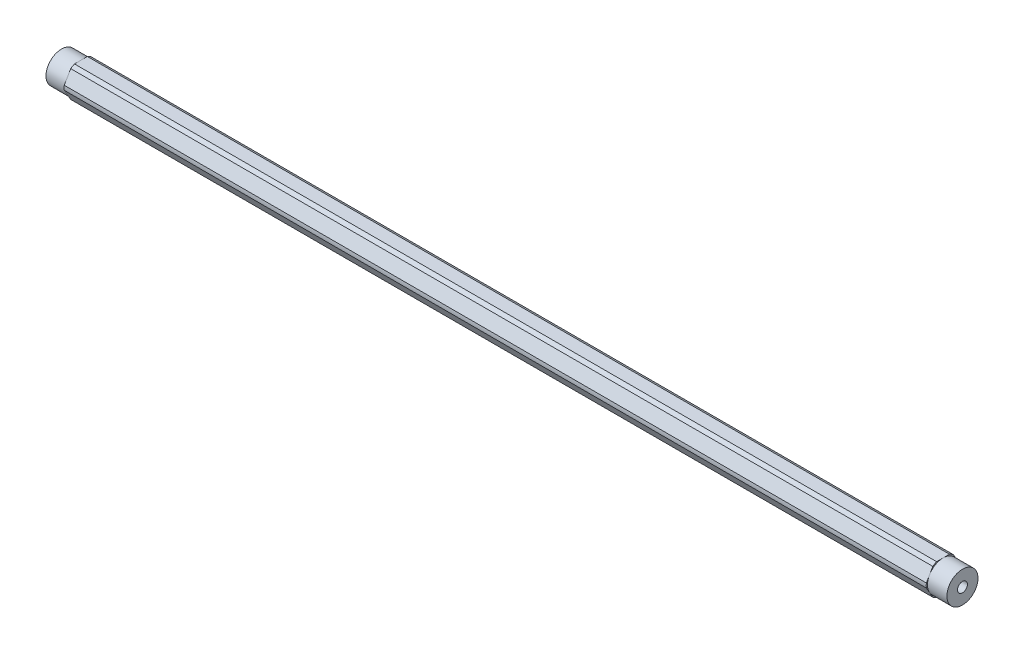
SolidWorks part; units mm, degrees
material "7075-T6 (SN)"
ref_plane "Front Plane" through (0, 0, 0) normal (0, 0, 1) x (1, 0, 0)
ref_plane "Top Plane" through (0, 0, 0) normal (0, 1, 0) x (1, 0, 0)
ref_plane "Right Plane" through (0, 0, 0) normal (1, 0, 0) x (0, 0, -1)
sketch "Sketch1" plane through (0, 0, 0) normal (1, 0, 0) x (0, 0, -1)
  line L1 (7.3323, 0) -> (3.6662, 6.35)
  line L2 (3.6662, 6.35) -> (-3.6662, 6.35)
  line L3 (-3.6662, 6.35) -> (-7.3323, 0)
  line L4 (-7.3323, 0) -> (-3.6662, -6.35)
  line L5 (-3.6662, -6.35) -> (3.6662, -6.35)
  line L6 (3.6662, -6.35) -> (7.3323, 0)
  circle A0 centre (0, 0) radius 6.875
  circle A1 centre (0, 0) radius 2.0193
  circle A2 centre (0, 0) radius 6.35 construction
  dimension "D1" = 12.7
  dimension "D2" = 13.75
  dimension "D3" = 4.0386
extrude "Boss-Extrude1" add sketch "Sketch1" along normal mid plane 368.3 contours L1 A0 L2 L3 L4 L5 L6 A1 region at (0, 0.4353, -6.6736)
sketch "Sketch2" plane through (184.15, 0, 0) normal (1, 0, 0) x (0, 0, -1)
  circle A0 centre (0, 0) radius 6.35
  dimension "D1" = 12.7
extrude "Cut-Extrude-Thin1" cut sketch "Sketch2" against normal blind 7.9375 thin thin type one direction wall 2.54
mirror "Mirror1" about plane through (0, 0, 0) normal (1, 0, 0) of "Cut-Extrude-Thin1"
equation "\"D2@Sketch1\"=13.75mm"
